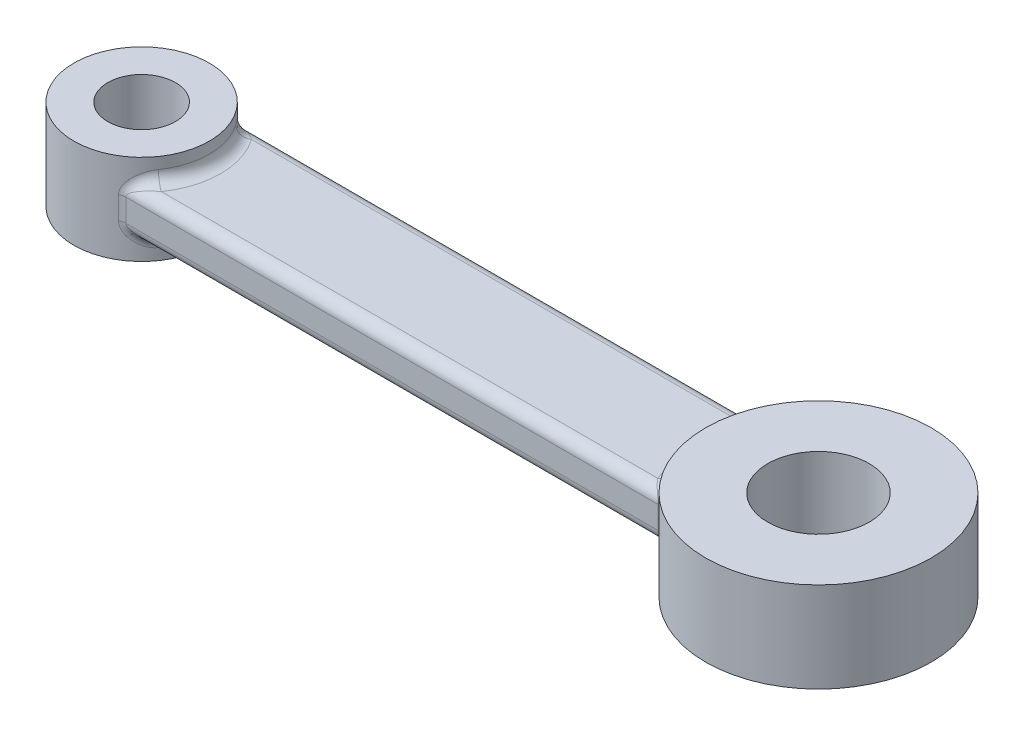
SolidWorks part; units mm, degrees
ref_plane "Front Plane" through (0, 0, 0) normal (0, 0, 1) x (1, 0, 0)
ref_plane "Top Plane" through (0, 0, 0) normal (0, 1, 0) x (1, 0, 0)
ref_plane "Right Plane" through (0, 0, 0) normal (1, 0, 0) x (0, 0, -1)
sketch "Sketch1" plane through (0, 0, 0) normal (0, 1, 0) x (1, 0, 0)
  line L1 (-15, 2.5) -> (15, 2.5)
  line L2 (-15, 2.5) -> (-15, -2.5)
  line L3 (-15, -2.5) -> (15, -2.5)
  line L4 (15, 2.5) -> (15, -2.5)
  line L5 (-15, 2.5) -> (15, -2.5) construction
  line L6 (-15, -2.5) -> (15, 2.5) construction
  point P0 (0, 0)
  dimension "D1" = 30
  dimension "D2" = 5
extrude "Boss-Extrude1" add sketch "Sketch1" along normal mid plane 2
sketch "Sketch2" plane through (0, 0, 0) normal (0, 1, 0) x (1, 0, 0)
  line L0 (-15, 2.5) -> (-15, -2.5) construction
  line L1 (15, -2.5) -> (15, 2.5) construction
  circle A0 centre (-15, 0) radius 3
  circle A1 centre (15, 0) radius 5
  dimension "D1" = 6
  dimension "D2" = 10
extrude "Boss-Extrude2" add sketch "Sketch2" along normal mid plane 4
sketch "Sketch3" plane through (0, 2, 0) normal (0, 1, 0) x (1, 0, 0)
  line L0 (0, 0) -> (-15, 0) construction
  circle A0 centre (-15, 0) radius 1.5
  dimension "D1" = 3
extrude "Cut-Extrude1" cut sketch "Sketch3" against normal through all
sketch "Sketch4" plane through (0, 2, 0) normal (0, 1, 0) x (1, 0, 0)
  line L0 (0, 0) -> (15, 0) construction
  circle A0 centre (15, 0) radius 2.25
  dimension "D1" = 4.5
extrude "Cut-Extrude2" cut sketch "Sketch4" against normal through all
fillet "Fillet1" radius 0.5 12 edges at (10, -1, 0) (-12, -1, 0) (10.6699, 0, 2.5) (10.6699, 0, -2.5) (-13.3417, 0, -2.5) (-13.3417, 0, 2.5) (10, 1, 0) (-12, 1, 0) (-1.3359, -1, -2.5) (-1.3359, 1, -2.5) (-1.3359, -1, 2.5) (-1.3359, 1, 2.5)
